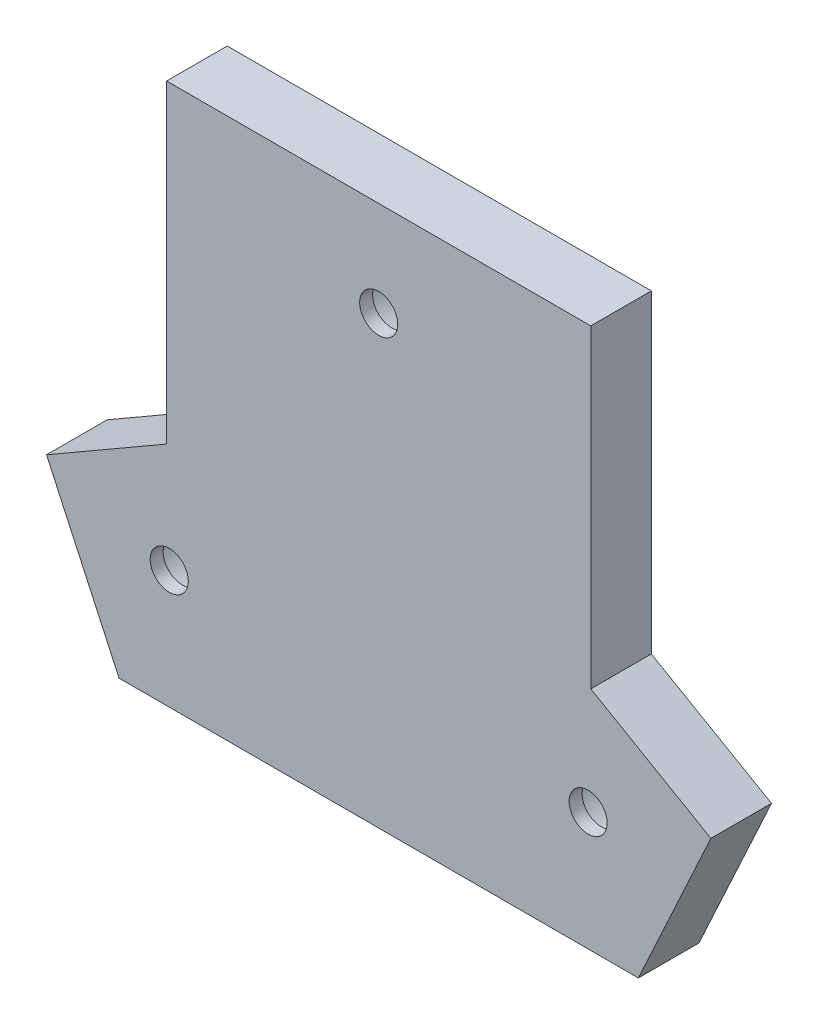
SolidWorks part; units mm, degrees
ref_plane "Front Plane" through (0, 0, 0) normal (0, 0, 1) x (1, 0, 0)
ref_plane "Top Plane" through (0, 0, 0) normal (0, 1, 0) x (1, 0, 0)
ref_plane "Right Plane" through (0, 0, 0) normal (1, 0, 0) x (0, 0, -1)
sketch "Sketch1" plane through (0, 0, 0) normal (0, 0, 1) x (1, 0, 0)
  line L0 (5.5, 62.5) -> (5.5, 26.173)
  line L1 (5.5, 26.173) -> (-8.3768, 18.1612)
  line L2 (-8.3768, 18.1612) -> (0, 0)
  line L3 (0, 0) -> (60, 0)
  line L4 (60, 0) -> (68.3768, 18.1612)
  line L5 (68.3768, 18.1612) -> (54.5, 26.173)
  line L6 (54.5, 26.173) -> (54.5, 62.5)
  line L7 (54.5, 62.5) -> (5.5, 62.5)
  line L8 (23.9995, 44.4998) -> (35.9991, 58.5002) construction
  line L9 (1.9569, 5.3076) -> (9.6436, 22.0681) construction
  line L10 (50.3566, 22.0692) -> (58.0442, 5.3091) construction
  circle A0 centre (54.2004, 13.6891) radius 5.1
  circle A1 centre (5.8002, 13.6879) radius 5.1
  circle A2 centre (29.9993, 51.5) radius 5.1
  circle A3 centre (29.9993, 51.5) radius 2.2
  circle A4 centre (54.2004, 13.6891) radius 2.2
  circle A5 centre (5.8002, 13.6879) radius 2.2
  dimension "D1" = 10.2
  dimension "D2" = 4.4
extrude "Boss-Extrude1" add sketch "Sketch1" along normal blind 7 contours L6 L7 L0 L1 L2 L3 L4 L5 A2 A1 A0 | A1 A5 | A5 | A0 A4 | A4 | A2 A3 | A3 region at (30, 29.0296, 0) region at (49.2446, 13.6891, 0) region at (0.8445, 13.6879, 0) region at (25.0435, 51.5, 0) region at (29.9993, 51.5, 0) region at (54.2004, 13.6891, 0) region at (5.8002, 13.6879, 0)
extrude "Cut-Extrude1" cut sketch "Sketch1<3>" along normal offset from surface (5.5 mm away) 1.5 contours A2 A3 | A0 A4 | A1 A5 region at (49.2446, 13.6891, 0) region at (0.8445, 13.6879, 0) region at (25.0435, 51.5, 0) up to face at (30, 26.7085, 7)
sketch "Sketch1<3>" plane through (0, 0, 0) normal (0, 0, 1) x (1, 0, 0) same geometry as "Sketch1"
extrude "Cut-Extrude2" cut sketch "Sketch1<4>" along normal up to surface (7 mm away) contours A4 | A5 | A3 region at (29.9993, 51.5, 0) region at (54.2004, 13.6891, 0) region at (5.8002, 13.6879, 0) up to face at (30, 26.7085, 7)
sketch "Sketch1<4>" plane through (0, 0, 0) normal (0, 0, 1) x (1, 0, 0) same geometry as "Sketch1"
